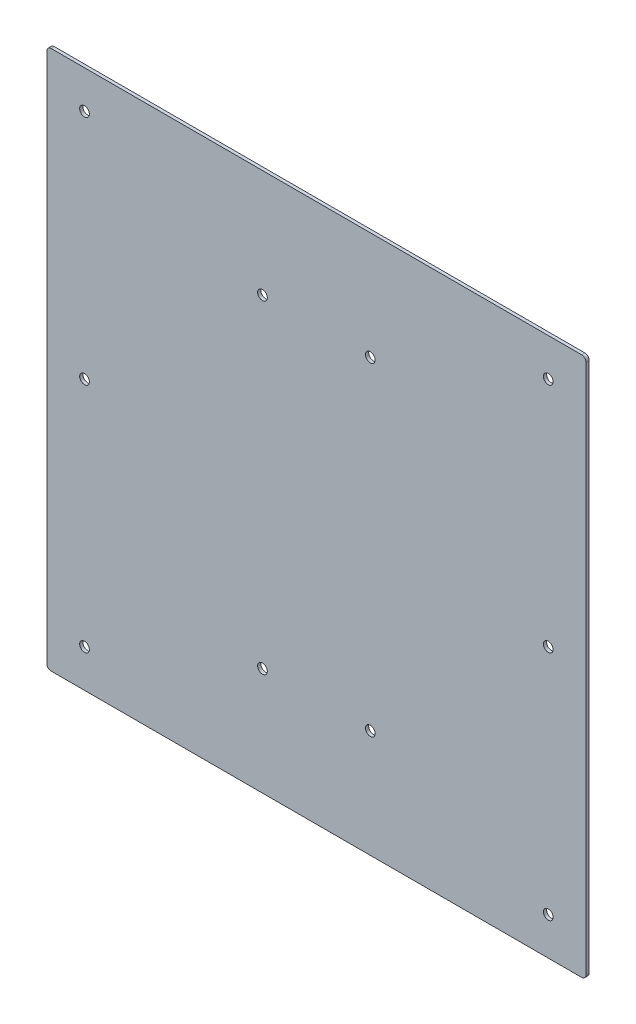
SolidWorks part; units mm, degrees
ref_plane "Front Plane" through (0, 0, 0) normal (0, 0, 1) x (1, 0, 0)
ref_plane "Top Plane" through (0, 0, 0) normal (0, 1, 0) x (1, 0, 0)
ref_plane "Right Plane" through (0, 0, 0) normal (1, 0, 0) x (0, 0, -1)
sketch "Sketch1" plane through (0, 0, 0) normal (0, 0, 1) x (1, 0, 0)
  line L1 (-125, -125) -> (125, -125)
  line L2 (-125, -125) -> (-125, 125)
  line L3 (-125, 125) -> (125, 125)
  line L4 (125, -125) -> (125, 125)
  line L5 (-125, -125) -> (125, 125) construction
  line L6 (-125, 125) -> (125, -125) construction
  circle A0 centre (-25, 75) radius 2.25
  circle A1 centre (25, 75) radius 2.25
  circle A2 centre (25, -75) radius 2.25
  circle A3 centre (-25, -75) radius 2.25
  point P0 (0, 0)
  point P14 (0, 0)
  point P15 (0, 0)
  point P16 (0, 0)
  point P17 (0, 0)
  point P18 (37.2353, 76.5882)
  dimension "D1" = 150
  dimension "D7" = 4.5
  dimension "D2" = 50
  dimension "D3" = 25
  dimension "D4" = 75
  dimension "D5" = 250
  dimension "D6" = 250
extrude "Boss-Extrude1" add sketch "Sketch1" along normal blind 1.4986
fillet "Fillet1" radius 2 4 edges at (-125, -125, 0.7493) (125, -125, 0.7493) (125, 125, 0.7493) (-125, 125, 0.7493)
sketch "Sketch2" plane through (0, 0, 1.4986) normal (0, 0, 1) x (1, 0, 0)
  line L0 (-123, -125) -> (123, -125) construction
  line L1 (-125, 123) -> (-125, -123) construction
  line L2 (123, 125) -> (-123, 125) construction
  line L3 (125, -123) -> (125, 123) construction
  circle A0 centre (-107.5, 107.5) radius 2.25
  circle A1 centre (107.5, 107.5) radius 2.25
  circle A2 centre (107.5, -107.5) radius 2.25
  circle A3 centre (-107.5, -107.5) radius 2.25
  circle A4 centre (-107.5, 0) radius 2.25
  circle A5 centre (107.5, 0) radius 2.25
  point P10 (0, 0)
  point P11 (0, 0)
  point P12 (0, 0)
  point P13 (0, 0)
  point P14 (0, 0)
  point P15 (0, 0)
  point P16 (107.5, 13.2296)
  dimension "D1" = 4.5
  dimension "D2" = 17.5
  dimension "D3" = 17.5
  dimension "D4" = 17.5
  dimension "D5" = 17.5
extrude "Cut-Extrude1" cut sketch "Sketch2" against normal up to surface (1.4986 mm away) up to face at (27.25, -75, 0)
